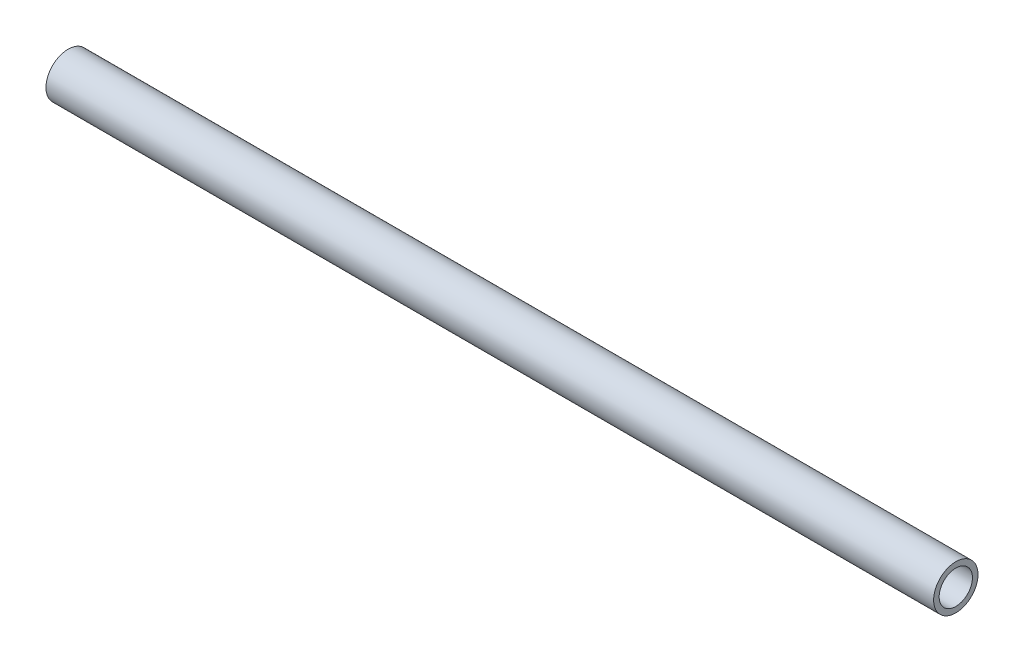
SolidWorks part; units mm, degrees
ref_plane "Front" through (0, 0, 0) normal (0, 0, 1) x (1, 0, 0)
ref_plane "Top" through (0, 0, 0) normal (0, 1, 0) x (1, 0, 0)
ref_plane "Right" through (0, 0, 0) normal (1, 0, 0) x (0, 0, -1)
sketch "Sketch1" plane through (0, 0, 0) normal (1, 0, 0) x (0, 0, -1)
  circle A0 centre (0, 0) radius 12.7
  circle A1 centre (0, 0) radius 9.525
  point P4 (12.7, 0)
  point P5 (9.525, 0)
  dimension "OD" = 25.4
  dimension "ID" = 19.05
  dimension "Wall" = 3.175
extrude "Extrude1" add sketch "Sketch1" along normal mid plane 914.4
sketch "Sketch2" plane through (0, 0, 0) normal (0, 0, 1) x (1, 0, 0)
  line L0 (-457.2, 0) -> (457.2, 0) construction
  line L1 (-457.2, 12.7) -> (-457.2, -12.7) construction
sketch "Sketch3" plane through (-457.2, 0, 0) normal (-1, 0, 0) x (0, 0, 1)
  circle A0 centre (0, 0) radius 12.7 construction
  circle A1 centre (0, 0) radius 9.525 construction
  circle A2 centre (0, 0) radius 12.7
  circle A3 centre (0, 0) radius 9.525
extrude "Cut-Extrude1" cut sketch "Sketch3" against normal offset from surface (406.4 mm away) 508 up to face at (457.2, 0, -12.7)
